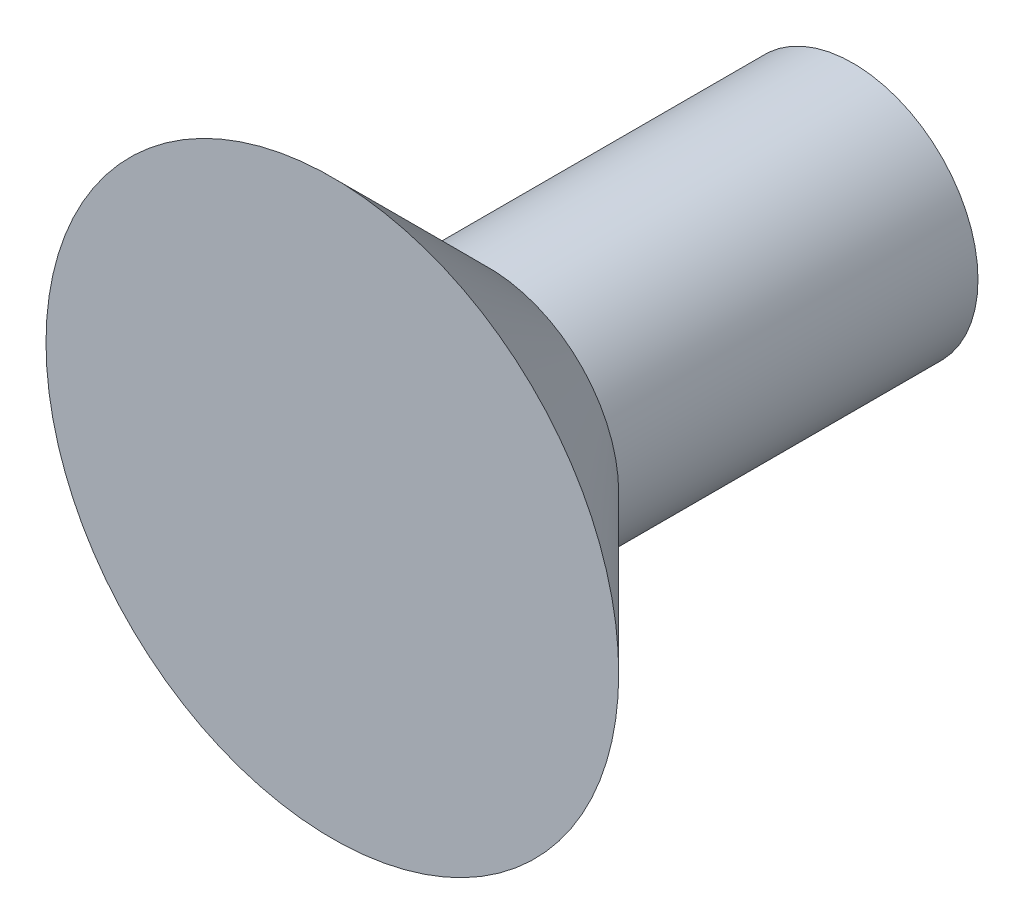
SolidWorks part; units mm, degrees
ref_plane "Ön Düzlem" through (0, 0, 0) normal (0, 0, 1) x (1, 0, 0)
ref_plane "Üst Düzlem" through (0, 0, 0) normal (0, 1, 0) x (1, 0, 0)
ref_plane "Sağ Düzlem" through (0, 0, 0) normal (1, 0, 0) x (0, 0, -1)
sketch "Çizim1" plane through (0, 0, 0) normal (0, 0, 1) x (1, 0, 0)
  circle A0 centre (0, 0) radius 2.4
  dimension "D1" = 4.8
extrude "Yükseklik-Ekstrüzyon1" add sketch "Çizim1" along normal blind 7
sketch "Çizim2" plane through (0, 0, 7) normal (0, 0, 1) x (1, 0, 0)
  circle A0 centre (0, 0) radius 2.5
extrude "Yükseklik-Ekstrüzyon2" add sketch "Çizim2" along normal blind 3 draft 45 draft outward yes
